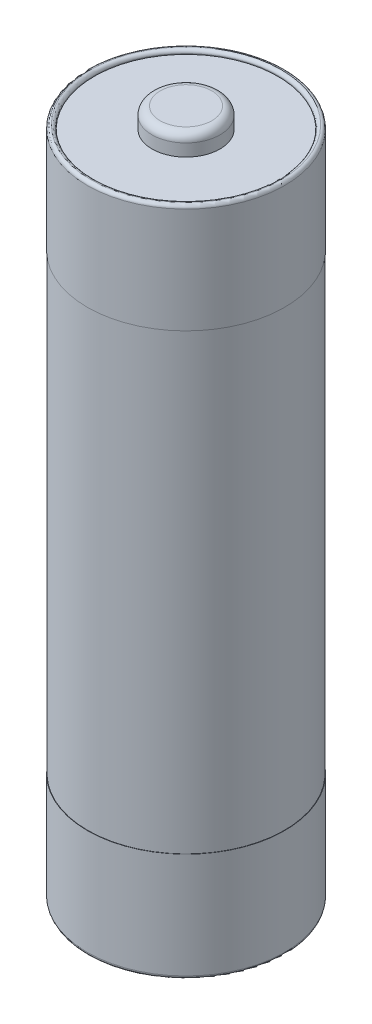
SolidWorks part; units mm, degrees
ref_plane "Front Plane" through (0, 0, 0) normal (0, 0, 1) x (1, 0, 0)
ref_plane "Top Plane" through (0, 0, 0) normal (0, 1, 0) x (1, 0, 0)
ref_plane "Right Plane" through (0, 0, 0) normal (1, 0, 0) x (0, 0, -1)
sketch "Sketch1" plane through (0, 0, 0) normal (0, 1, 0) x (1, 0, 0)
  circle A0 centre (0, 0) radius 7.25
  dimension "D1" = 14.5
extrude "Boss-Extrude1" add sketch "Sketch1" along normal blind 8
sketch "Sketch2" plane through (0, 8, 0) normal (0, 1, 0) x (1, 0, 0)
  circle A0 centre (0, 0) radius 7.225
  dimension "D1" = 14.45
extrude "Boss-Extrude2" add sketch "Sketch2" along normal blind 33.3
sketch "Sketch3" plane through (0, 41.3, 0) normal (0, 1, 0) x (1, 0, 0)
  circle A0 centre (0, 0) radius 7.25
  dimension "D1" = 14.5
extrude "Boss-Extrude3" add sketch "Sketch3" along normal blind 8
sketch "Sketch4" plane through (0, 49.3, 0) normal (0, 1, 0) x (1, 0, 0)
  circle A0 centre (0, 0) radius 6.75
  dimension "D1" = 13.5
extrude "Cut-Extrude1" cut sketch "Sketch4" against normal blind 0.3
sketch "Sketch5" plane through (0, 49, 0) normal (0, 1, 0) x (1, 0, 0)
  circle A0 centre (0, 0) radius 2.5
  dimension "D1" = 5
extrude "Boss-Extrude4" add sketch "Sketch5" along normal blind 1.5
sketch "Sketch6" plane through (0, 0, 0) normal (0, -1, 0) x (1, 0, 0)
  circle A0 centre (0, 0) radius 6.75
  dimension "D1" = 13.5
extrude "Cut-Extrude2" cut sketch "Sketch6" against normal blind 0.3
sketch "Sketch7" plane through (0, 0.3, 0) normal (0, -1, 0) x (1, 0, 0)
  circle A0 centre (0, 0) radius 3.5
  dimension "D1" = 7
extrude "Boss-Extrude5" add sketch "Sketch7" along normal blind 0.7
fillet "Fillet1" radius 0.6 1 edges at (0, 50.5, 2.5)
fillet "Fillet3" radius 0.25 4 edges at (0, 49.3, 7.25) (0, 49.3, 6.75) (0, 0, 7.25) (0, 0, -6.75)
fillet "Fillet4" radius 0.4 1 edges at (0, -0.4, -3.5)
fillet "Fillet5" radius 0.4 1 edges at (0, 0.3, -3.5)
